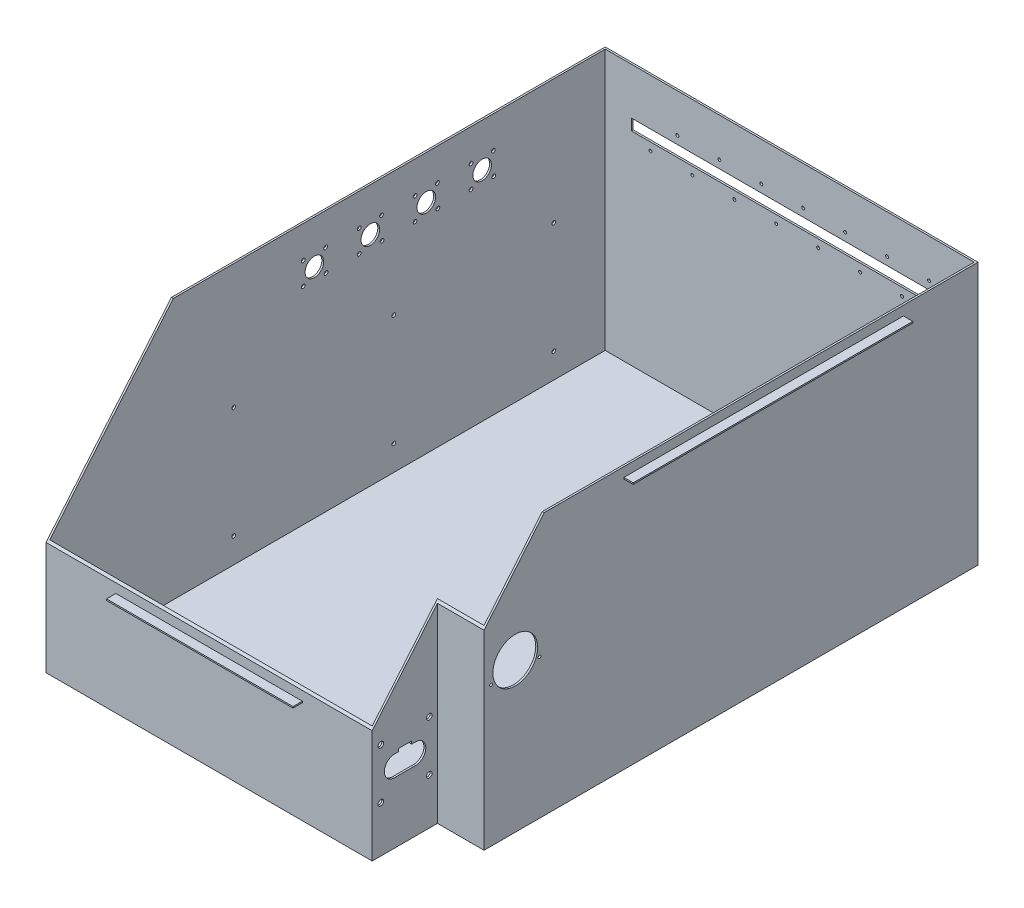
SolidWorks part; units mm, degrees
ref_plane "Front Plane" through (0, 0, 0) normal (0, 0, 1) x (1, 0, 0)
ref_plane "Top Plane" through (0, 0, 0) normal (0, 1, 0) x (1, 0, 0)
ref_plane "Right Plane" through (0, 0, 0) normal (1, 0, 0) x (0, 0, -1)
sketch "Sketch1" plane through (0, 0, 0) normal (0, 1, 0) x (1, 0, 0)
  line L1 (-200, 237.8263) -> (200, 237.8263)
  line L2 (-200, 237.8263) -> (-200, -362.1737)
  line L3 (-200, -362.1737) -> (150, -362.1737)
  line L4 (200, 237.8263) -> (200, -292.1737)
  line L6 (200, -292.1737) -> (150, -292.1737)
  line L7 (150, -292.1737) -> (150, -362.1737)
  line L8 (0, -55) -> (0, 55) construction
  point P1 (0, 237.8263)
  dimension "D1" = 600
  dimension "D2" = 400
  dimension "D5" = 70
  dimension "D6" = 50
extrude "Boss-Extrude1" add sketch "Sketch1" along normal blind 1.5
sketch "Sketch2" plane through (0, 1.5, 0) normal (0, 1, 0) x (1, 0, 0)
  line L60 (-198, 235.8263) -> (-198, -360.1737)
  line L61 (-198, -360.1737) -> (148, -360.1737)
  line L62 (148, -360.1737) -> (148, -290.1737)
  line L63 (148, -290.1737) -> (198, -290.1737)
  line L64 (198, -290.1737) -> (198, 235.8263)
  line L65 (198, 235.8263) -> (-198, 235.8263)
  line L66 (-200, 237.8263) -> (-200, -362.1737)
  line L67 (-200, -362.1737) -> (150, -362.1737)
  line L68 (150, -362.1737) -> (150, -292.1737)
  line L69 (150, -292.1737) -> (200, -292.1737)
  line L70 (200, -292.1737) -> (200, 237.8263)
  line L71 (200, 237.8263) -> (-200, 237.8263)
  line L72 (-200, 237.8263) -> (-200, -362.1737)
  line L73 (-200, -362.1737) -> (150, -362.1737)
  line L74 (150, -362.1737) -> (150, -292.1737)
  line L75 (150, -292.1737) -> (200, -292.1737)
  line L76 (200, -292.1737) -> (200, 237.8263)
  line L77 (200, 237.8263) -> (-200, 237.8263)
  dimension "D3" = 2
  dimension "D4" = 2
  dimension "D2" = 2
  dimension "D5" = 2
  dimension "D6" = 2
  dimension "D1" = 0
extrude "Boss-Extrude2" add sketch "Sketch2" along normal blind 280
sketch "Sketch3" plane through (-200, 0, 0) normal (-1, 0, 0) x (0, 0, 1)
  line L3 (362.1737, 281.5) -> (362.1737, 0) construction
  line L4 (362.1737, 121.1176) -> (227.5969, 281.5)
  line L6 (-237.8263, 281.5) -> (362.1737, 281.5) construction
  line L9 (362.1737, 281.5) -> (362.1737, 121.1176)
  line L10 (227.5969, 281.5) -> (362.1737, 281.5)
  dimension "D1" = 50
sketch "Sketch4" plane through (0, 0, -237.8263) normal (0, 0, -1) x (-1, 0, 0)
  line L0 (-200, 281.5) -> (-200, 0) construction
  line L1 (-200, 234.6761) -> (200, 234.6761)
  line L2 (-200, 234.6761) -> (-200, 192.2905)
  line L3 (-200, 192.2905) -> (200, 192.2905)
  line L4 (200, 234.6761) -> (200, 192.2905)
  line L5 (200, 281.5) -> (200, 0) construction
extrude "Boss-Extrude3" add sketch "Sketch4" against normal blind 2
extrude "Cut-Extrude1" cut sketch "Sketch3" against normal through all both and the other way through all
sketch "Sketch5" plane through (-200, 0, 0) normal (-1, 0, 0) x (0, 0, 1)
  line L0 (-115.8263, 223.1206) -> (-115.8263, 247.1206) construction
  line L5 (-115.8263, 223.1206) -> (-91.8263, 223.1206) construction
  line L6 (-115.8263, 247.1206) -> (-91.8263, 247.1206) construction
  line L7 (-91.8263, 223.1206) -> (-91.8263, 247.1206) construction
  line L8 (-115.8263, 223.1206) -> (-91.8263, 247.1206) construction
  line L9 (-115.8263, 247.1206) -> (-91.8263, 223.1206) construction
  line L10 (-55.8263, 223.1206) -> (-55.8263, 247.1206) construction
  line L11 (-55.8263, 223.1206) -> (-31.8263, 223.1206) construction
  line L12 (-55.8263, 247.1206) -> (-31.8263, 247.1206) construction
  line L13 (-31.8263, 223.1206) -> (-31.8263, 247.1206) construction
  line L14 (-55.8263, 223.1206) -> (-31.8263, 247.1206) construction
  line L15 (-55.8263, 247.1206) -> (-31.8263, 223.1206) construction
  line L16 (4.1737, 223.1206) -> (4.1737, 247.1206) construction
  line L17 (4.1737, 223.1206) -> (28.1737, 223.1206) construction
  line L18 (4.1737, 247.1206) -> (28.1737, 247.1206) construction
  line L19 (28.1737, 223.1206) -> (28.1737, 247.1206) construction
  line L20 (4.1737, 223.1206) -> (28.1737, 247.1206) construction
  line L21 (4.1737, 247.1206) -> (28.1737, 223.1206) construction
  line L22 (64.1737, 223.1206) -> (64.1737, 247.1206) construction
  line L23 (64.1737, 223.1206) -> (88.1737, 223.1206) construction
  line L24 (64.1737, 247.1206) -> (88.1737, 247.1206) construction
  line L25 (88.1737, 223.1206) -> (88.1737, 247.1206) construction
  line L26 (64.1737, 223.1206) -> (88.1737, 247.1206) construction
  line L27 (64.1737, 247.1206) -> (88.1737, 223.1206) construction
  line L28 (-235.8263, 281.5) -> (-235.8263, 1.5) construction
  circle A0 centre (-115.8263, 247.1206) radius 2
  circle A1 centre (-116.3263, 223.1259) radius 2
  circle A2 centre (-91.8263, 223.1206) radius 2
  circle A3 centre (-91.8263, 247.1206) radius 2
  circle A4 centre (-103.8263, 235.1206) radius 10
  circle A5 centre (-55.8263, 247.1206) radius 2
  circle A6 centre (-56.3263, 223.1259) radius 2
  circle A7 centre (-31.8263, 223.1206) radius 2
  circle A8 centre (-31.8263, 247.1206) radius 2
  circle A9 centre (-43.8263, 235.1206) radius 10
  circle A10 centre (4.1737, 247.1206) radius 2
  circle A11 centre (3.6737, 223.1259) radius 2
  circle A12 centre (28.1737, 223.1206) radius 2
  circle A13 centre (28.1737, 247.1206) radius 2
  circle A14 centre (16.1737, 235.1206) radius 10
  circle A15 centre (64.1737, 247.1206) radius 2
  circle A16 centre (63.6737, 223.1259) radius 2
  circle A17 centre (88.1737, 223.1206) radius 2
  circle A18 centre (88.1737, 247.1206) radius 2
  circle A19 centre (76.1737, 235.1206) radius 10
  point P9 (-103.8263, 235.1206)
  point P24 (-43.8263, 235.1206)
  point P38 (16.1737, 235.1206)
  point P52 (76.1737, 235.1206)
  dimension "D2" = 20
  dimension "D5" = 4
  dimension "D1" = 24
  dimension "D3" = 24
  dimension "D4" = 24
  dimension "D7" = 120
  dimension "D6" = 4
sketch "Sketch6" plane through (-198, 0, 0) normal (1, 0, 0) x (0, 0, -1)
  arc A0 (151.1392, 167.4539) -> (156.7272, 167.4539) centre (153.9332, 167.4539) ccw construction
  arc A1 (-68.8756, 167.4539) -> (-63.2876, 167.4539) centre (-66.0816, 167.4539) ccw construction
  arc A2 (-178.883, 167.4539) -> (-173.295, 167.4539) centre (-176.089, 167.4539) ccw construction
  arc A3 (151.1392, 167.4539) -> (156.7272, 167.4539) centre (153.9332, 167.4539) ccw
  arc A4 (-68.8756, 167.4539) -> (-63.2876, 167.4539) centre (-66.0816, 167.4539) ccw
  arc A5 (-178.883, 167.4539) -> (-173.295, 167.4539) centre (-176.089, 167.4539) ccw
  circle A6 centre (-176.089, 167.4539) radius 2.794
  circle A7 centre (-176.089, 167.4539) radius 4.5
  circle A8 centre (-64.4633, 167.4539) radius 4.5
  circle A9 centre (-64.4633, 167.4539) radius 2.794
  circle A10 centre (155.5515, 167.4539) radius 2.794
  circle A11 centre (155.5515, 167.4539) radius 4.5
  dimension "D1" = 9
extrude "Boss-Extrude4" [suppressed] add sketch "Sketch6" along normal blind 50 contours A4 A9 | A8 | A7 | A6 | A11 | A10
sketch "Sketch8" plane through (-198, 0, 0) normal (1, 0, 0) x (0, 0, -1)
  line L0 (235.8263, 1.5) -> (-360.1737, 1.5) construction
  line L1 (-360.1737, 123.5011) -> (-360.1737, 1.5) construction
  circle A0 centre (-265.6737, 172.1992) radius 2.39
  circle A1 centre (-265.6737, 172.1992) radius 4.39
  circle A2 centre (-265.1737, 16.5) radius 2.39
  circle A3 centre (-265.1737, 16.5) radius 4.39
  dimension "D3" = 4.78
  dimension "D4" = 2
  dimension "D1" = 155.7
  dimension "D2" = 15
  dimension "D5" = 95
extrude "Boss-Extrude5" [suppressed] add sketch "Sketch8" along normal blind 15
sketch "Sketch10" plane through (148, 0, 0) normal (-1, 0, 0) x (0, 0, 1)
  line L0 (315.6737, 86.5) -> (320.9237, 86.5) construction
  line L1 (315.6737, 66.5) -> (338.1737, 66.5) construction
  line L2 (338.1737, 76.5) -> (315.6737, 76.5) construction
  line L3 (360.1737, 1.5) -> (290.1737, 1.5) construction
  line L5 (320.9237, 86.5) -> (320.9237, 89.5) construction
  line L6 (320.9237, 89.5) -> (332.9237, 89.5) construction
  line L7 (332.9237, 86.5) -> (332.9237, 89.5) construction
  line L8 (360.1737, 123.5011) -> (360.1737, 1.5) construction
  line L9 (332.9237, 86.5) -> (338.1737, 86.5) construction
  line L10 (319.9237, 90.5) -> (333.9237, 90.5)
  line L11 (333.9237, 87.5) -> (333.9237, 90.5)
  line L12 (333.9237, 87.5) -> (338.1737, 87.5)
  line L13 (315.6737, 65.5) -> (338.1737, 65.5)
  line L14 (315.6737, 87.5) -> (319.9237, 87.5)
  line L15 (319.9237, 87.5) -> (319.9237, 90.5)
  line L17 (300.9737, 49.55) -> (352.8737, 49.55) construction
  line L18 (300.9737, 49.55) -> (300.9737, 103.45) construction
  line L19 (300.9737, 103.45) -> (352.8737, 103.45) construction
  line L20 (352.8737, 49.55) -> (352.8737, 103.45) construction
  line L21 (300.9737, 49.55) -> (352.8737, 103.45) construction
  line L22 (300.9737, 103.45) -> (352.8737, 49.55) construction
  arc A0 (315.6737, 86.5) -> (315.6737, 66.5) centre (315.6737, 76.5) ccw construction
  arc A1 (338.1737, 66.5) -> (338.1737, 86.5) centre (338.1737, 76.5) ccw construction
  arc A2 (338.1737, 65.5) -> (338.1737, 87.5) centre (338.1737, 76.5) ccw
  arc A3 (315.6737, 87.5) -> (315.6737, 65.5) centre (315.6737, 76.5) ccw
  circle A4 centre (300.9737, 103.45) radius 3
  circle A5 centre (352.8737, 103.45) radius 3
  circle A6 centre (300.9737, 49.55) radius 3
  circle A7 centre (352.8737, 49.55) radius 3
  point P12 (326.9237, 89.5)
  point P13 (326.9237, 76.5)
  point P26 (326.9237, 76.5)
  dimension "D1" = 65
  dimension "D2" = 22.5
  dimension "D6" = 20
  dimension "D10" = 6
  dimension "D3" = 22
  dimension "D4" = 12
  dimension "D5" = 3
  dimension "D8" = 51.9
  dimension "D9" = 53.9
  dimension "D7" = 1
extrude "Cut-Extrude2" cut sketch "Sketch10" against normal up to surface (2 mm away) contours L0 L7 L6 L5 | L2 A1 L0 A0 | A1 L2 A0 L1 | A0 | A1 | L14 A3 L13 A2 L12 L11 L10 L15 | A4 | A5 | A7 | A6 region at (148, 77.0724, 326.9237) region at (148, 103.45, 300.9737) region at (148, 103.45, 352.8737) region at (148, 49.55, 352.8737) up to face at (150, 81.4145, 327.1737)
sketch "Sketch11" plane through (148, 0, 0) normal (-1, 0, 0) x (0, 0, 1)
  line L0 (298.4737, 103.43) -> (298.4737, 49.53) construction
  line L13 (315.6737, 66.5) -> (338.1737, 66.5) construction
  line L14 (315.6737, 86.5) -> (320.9237, 86.5) construction
  line L15 (315.6737, 66.5) -> (338.1737, 66.5)
  line L19 (315.6737, 86.5) -> (318.4237, 86.5)
  line L20 (333.9237, 90.5) -> (319.9237, 90.5)
  line L21 (333.9237, 90.5) -> (319.9237, 90.5)
  line L22 (333.9237, 87.5) -> (333.9237, 90.5)
  line L23 (333.9237, 87.5) -> (333.9237, 90.5)
  line L28 (330.4237, 86.5) -> (320.9237, 86.5)
  line L29 (315.7815, 66) -> (338.2021, 66)
  line L30 (330.9237, 86) -> (320.2852, 86)
  line L31 (330.9237, 86) -> (330.9237, 91)
  line L32 (330.9237, 91) -> (317.9237, 91)
  line L33 (317.9237, 91) -> (317.9237, 87)
  line L34 (315.7815, 87) -> (317.9237, 87)
  line L36 (298.4737, 103.43) -> (350.3737, 103.43) construction
  line L43 (333.9237, 90.5) -> (319.9237, 90.5)
  line L44 (333.9237, 90.5) -> (319.9237, 90.5)
  line L45 (333.9237, 87.5) -> (333.9237, 90.5)
  line L46 (333.9237, 87.5) -> (333.9237, 90.5)
  line L47 (338.1737, 87.5) -> (333.9237, 87.5)
  line L48 (338.1737, 87.5) -> (333.9237, 87.5)
  line L49 (315.6737, 65.5) -> (338.1737, 65.5)
  line L50 (315.6737, 65.5) -> (338.1737, 65.5)
  line L51 (319.9237, 87.5) -> (315.6737, 87.5)
  line L52 (319.9237, 87.5) -> (315.6737, 87.5)
  line L53 (319.9237, 90.5) -> (319.9237, 87.5)
  line L54 (319.9237, 90.5) -> (319.9237, 87.5)
  line L55 (333.9237, 90.5) -> (319.9237, 90.5)
  line L56 (333.9237, 90.5) -> (319.9237, 90.5)
  line L57 (333.9237, 87.5) -> (333.9237, 90.5)
  line L58 (333.9237, 87.5) -> (333.9237, 90.5)
  line L59 (338.1737, 87.5) -> (333.9237, 87.5)
  line L60 (338.1737, 87.5) -> (333.9237, 87.5)
  line L61 (315.6737, 65.5) -> (338.1737, 65.5)
  line L62 (315.6737, 65.5) -> (338.1737, 65.5)
  line L63 (319.9237, 87.5) -> (315.6737, 87.5)
  line L64 (319.9237, 87.5) -> (315.6737, 87.5)
  line L65 (319.9237, 90.5) -> (319.9237, 87.5)
  line L66 (319.9237, 90.5) -> (319.9237, 87.5)
  line L67 (330.4237, 86.5) -> (330.4237, 90.5) construction
  line L68 (330.4237, 90.5) -> (318.4237, 90.5) construction
  line L69 (318.4237, 90.5) -> (318.4237, 86.5) construction
  line L70 (338.1737, 87.5) -> (333.9237, 87.5)
  line L71 (338.1737, 87.5) -> (333.9237, 87.5)
  line L72 (315.6737, 65.5) -> (338.1737, 65.5)
  line L73 (315.6737, 65.5) -> (338.1737, 65.5)
  line L74 (319.9237, 87.5) -> (315.6737, 87.5)
  line L75 (319.9237, 87.5) -> (315.6737, 87.5)
  line L76 (319.9237, 90.5) -> (319.9237, 87.5)
  line L77 (319.9237, 90.5) -> (319.9237, 87.5)
  arc A4 (338.2021, 66) -> (320.2852, 86) centre (336.3485, 82.3648) ccw
  arc A5 (338.1737, 65.5) -> (338.1737, 87.5) centre (338.1737, 76.5) ccw
  arc A7 (338.1737, 65.5) -> (338.1737, 87.5) centre (338.1737, 76.5) ccw
  arc A9 (315.7815, 87) -> (315.7815, 66) centre (311.0911, 76.5) ccw
  circle A10 centre (298.4737, 103.43) radius 3
  circle A11 centre (298.4737, 49.53) radius 3
  circle A12 centre (350.3737, 103.43) radius 3
  circle A13 centre (350.3737, 49.53) radius 3
  arc A16 (338.1737, 66.5) -> (320.9237, 86.5) centre (336.3485, 82.3648) ccw construction
  arc A17 (338.1737, 65.5) -> (338.1737, 87.5) centre (338.1737, 76.5) ccw
  arc A18 (315.6737, 87.5) -> (315.6737, 65.5) centre (315.6737, 76.5) ccw
  arc A19 (315.6737, 87.5) -> (315.6737, 65.5) centre (315.6737, 76.5) ccw
  arc A20 (315.6737, 86.5) -> (315.6737, 66.5) centre (311.0911, 76.5) ccw construction
  arc A21 (338.1737, 65.5) -> (338.1737, 87.5) centre (338.1737, 76.5) ccw
  arc A22 (315.6737, 87.5) -> (315.6737, 65.5) centre (315.6737, 76.5) ccw
  arc A23 (315.6737, 87.5) -> (315.6737, 65.5) centre (315.6737, 76.5) ccw
  arc A24 (338.1737, 65.5) -> (338.1737, 87.5) centre (338.1737, 76.5) ccw
  arc A25 (338.1737, 65.5) -> (338.1737, 87.5) centre (338.1737, 76.5) ccw
  arc A26 (315.6737, 87.5) -> (315.6737, 65.5) centre (315.6737, 76.5) ccw
  arc A27 (315.6737, 87.5) -> (315.6737, 65.5) centre (315.6737, 76.5) ccw
  dimension "D5" = 6
  dimension "D6" = 51.9
  dimension "D7" = 53.9
  dimension "D1" = 0
  dimension "D2" = 0
  dimension "D3" = 0
  dimension "D4" = 0.5
extrude "Cut-Extrude3" [suppressed] cut sketch "Sketch11" against normal through all
sketch "Sketch14" plane through (148, 0, 0) normal (-1, 0, 0) x (0, 0, 1)
  line L0 (362.1737, 121.1176) -> (362.1737, 0) construction
  line L1 (362.1737, 0) -> (292.1737, 0) construction
  circle A0 centre (297.2737, 103.43) radius 3
  circle A1 centre (349.1737, 103.43) radius 3
  circle A2 centre (349.1737, 49.53) radius 3
  circle A3 centre (297.2737, 49.53) radius 3
  dimension "D5" = 6
  dimension "D1" = 51.9
  dimension "D2" = 53.9
  dimension "D3" = 13
  dimension "D4" = 103.43
extrude "Cut-Extrude4" [suppressed] cut sketch "Sketch14" against normal up to surface (1.5 mm away) up to face at (150, 49.55, 303.9737)
sketch "Sketch15" plane through (198, 0, 0) normal (-1, 0, 0) x (0, 0, 1)
  line L1 (-223.8263, 252.1363) -> (-208.8263, 252.1363)
  line L2 (-223.8263, 252.1363) -> (-223.8263, 250.6363)
  line L3 (-223.8263, 250.6363) -> (-208.8263, 250.6363)
  line L4 (-208.8263, 252.1363) -> (-208.8263, 250.6363)
  line L5 (-235.8263, 281.5) -> (-235.8263, 1.5) construction
  line L6 (196.1737, 252.1363) -> (211.1737, 252.1363)
  line L7 (196.1737, 250.6363) -> (211.1737, 250.6363)
  line L8 (196.1737, 252.1363) -> (196.1737, 250.6363)
  line L9 (211.1737, 252.1363) -> (211.1737, 250.6363)
  dimension "D1" = 1.5
  dimension "D2" = 15
  dimension "D3" = 12
  dimension "D4" = 432
  dimension "D5" = 15
extrude "Boss-Extrude6" [suppressed] add sketch "Sketch15" along normal blind 15
ref_plane "Plane1" [suppressed] through (0, 0, -203.8263) normal (0, 0, -1) x (-1, 0, 0)
sketch "Sketch17" [suppressed] plane through (0, 0, -208.8263) normal (0, 0, 1) x (1, 0, 0)
  line L0 (198, 250.6363) -> (198, 235.6363)
  line L1 (198, 281.5) -> (198, 207.307) construction
  line L2 (198, 235.6363) -> (183, 250.6363)
  line L3 (183, 250.6363) -> (198, 250.6363)
  dimension "D1" = 15
extrude "Boss-Extrude7" [suppressed] add sketch "Sketch17" against normal blind 1.5
ref_plane "Plane2" [suppressed] through (0, 0, 191.1737) normal (0, 0, 1) x (1, 0, 0)
sketch "Sketch18" [suppressed] plane through (0, 0, 196.1737) normal (0, 0, 1) x (1, 0, 0)
  line L0 (198, 250.6363) -> (198, 235.6363)
  line L1 (198, 281.5) -> (198, 207.307) construction
  line L2 (198, 235.6363) -> (183, 250.6363)
  line L3 (183, 250.6363) -> (198, 250.6363)
  dimension "D1" = 15
extrude "Boss-Extrude8" [suppressed] add sketch "Sketch18" along normal blind 1.5
sketch "Sketch20" [suppressed] plane through (0, 252.1363, 0) normal (0, 1, 0) x (1, 0, 0)
  line L1 (183, 223.8263) -> (198, 223.8263) construction
  line L2 (183, 208.8263) -> (183, 223.8263) construction
  line L3 (183, -211.1737) -> (198, -211.1737) construction
  line L4 (183, -211.1737) -> (183, -196.1737) construction
  circle A0 centre (190.5, 216.3263) radius 2.4159
  circle A1 centre (190.5, -203.6737) radius 2
  dimension "D3" = 4
  dimension "D1" = 7.5
  dimension "D2" = 7.5
  dimension "D4" = 7.5
  dimension "D5" = 7.5
extrude "Cut-Extrude5" [suppressed] cut sketch "Sketch20" against normal up to surface (1.5 mm away)
extrude "Cut-Extrude7" cut sketch "Sketch5" against normal up to surface (2 mm away) up to face at (-198, 137.9002, 95.2583)
sketch "Sketch21" plane through (0, 0, -237.8263) normal (0, 0, -1) x (-1, 0, 0)
  line L0 (-200, 281.5) -> (200, 281.5) construction
  line L1 (-150, 271.5) -> (150, 271.5)
  line L2 (-150, 271.5) -> (-150, 270)
  line L3 (-150, 270) -> (150, 270)
  line L4 (150, 271.5) -> (150, 270)
  point P6 (0, 281.5)
  point P7 (0, 271.5)
  dimension "D1" = 1.5
  dimension "D2" = 300
  dimension "D3" = 10
extrude "Boss-Extrude9" add sketch "Sketch21" along normal blind 10
sketch "Sketch22" plane through (-200, 0, 0) normal (-1, 0, 0) x (0, 0, 1)
  line L0 (-237.8263, 281.5) -> (227.5969, 281.5) construction
  line L1 (-157.8263, 271.5) -> (142.1737, 271.5)
  line L2 (-157.8263, 271.5) -> (-157.8263, 270)
  line L3 (-157.8263, 270) -> (142.1737, 270)
  line L4 (142.1737, 271.5) -> (142.1737, 270)
  line L5 (-237.8263, 281.5) -> (-237.8263, 0) construction
  dimension "D1" = 1.5
  dimension "D2" = 10
  dimension "D3" = 80
  dimension "D4" = 300
extrude "Boss-Extrude10" add sketch "Sketch22" along normal blind 10
ref_plane "Plane3" through (0, 0, -77.8263) normal (0, 0, -1) x (-1, 0, 0)
sketch "Sketch23" plane through (0, 0, -77.8263) normal (0, 0, -1) x (-1, 0, 0)
  line L0 (210, 270) -> (200, 270) construction
  line L1 (210, 270) -> (200, 270)
  line L2 (210, 270) -> (200, 260)
  line L3 (200, 281.5) -> (200, 0) construction
  line L4 (200, 260) -> (200, 270)
  dimension "D1" = 10
extrude "Boss-Extrude11" add sketch "Sketch23" along normal mid plane 1.5
ref_plane "Plane4" through (0, 0, 52.1737) normal (0, 0, 1) x (1, 0, 0)
sketch "Sketch24" plane through (0, 0, 52.1737) normal (0, 0, 1) x (1, 0, 0)
  line L6 (-210, 270) -> (-200, 260)
  line L7 (-200, 260) -> (-200, 270)
  line L8 (-200, 270) -> (-210, 270)
  line L9 (-210, 270) -> (-200, 260)
  line L10 (-200, 260) -> (-200, 270)
  line L11 (-200, 270) -> (-210, 270)
  dimension "D1" = 0
extrude "Boss-Extrude12" add sketch "Sketch24" along normal mid plane 1.5
ref_plane "Plane5" through (100, 0, 0) normal (1, 0, 0) x (0, 0, -1)
sketch "Sketch25" plane through (100, 0, 0) normal (1, 0, 0) x (0, 0, -1)
  line L0 (247.8263, 270) -> (237.8263, 270)
  line L1 (237.8263, 270) -> (237.8263, 260)
  line L2 (237.8263, 281.5) -> (237.8263, 0) construction
  line L3 (237.8263, 260) -> (247.8263, 270)
  dimension "D1" = 10
extrude "Boss-Extrude13" add sketch "Sketch25" along normal mid plane 1.5
ref_plane "Plane6" through (-100, 0, 0) normal (-1, 0, 0) x (0, 0, 1)
sketch "Sketch26" plane through (-100, 0, 0) normal (-1, 0, 0) x (0, 0, 1)
  line L3 (-247.8263, 270) -> (-237.8263, 260)
  line L4 (-237.8263, 260) -> (-237.8263, 270)
  line L5 (-237.8263, 270) -> (-247.8263, 270)
  line L6 (-247.8263, 270) -> (-237.8263, 260)
  line L7 (-237.8263, 260) -> (-237.8263, 270)
  line L8 (-237.8263, 270) -> (-247.8263, 270)
  dimension "D1" = 0
extrude "Boss-Extrude14" add sketch "Sketch26" along normal mid plane 1.5
mirror "Mirror1" about plane through (0, 0, 0) normal (1, 0, 0) of "Boss-Extrude11", "Boss-Extrude12", "Boss-Extrude10"
sketch "Sketch27" plane through (0, 0, 362.1737) normal (0, 0, 1) x (1, 0, 0)
  line L0 (150, 121.1176) -> (-200, 121.1176) construction
  line L1 (-125, 111.1176) -> (75, 111.1176)
  line L2 (-125, 111.1176) -> (-125, 109.6176)
  line L3 (-125, 109.6176) -> (75, 109.6176)
  line L4 (75, 111.1176) -> (75, 109.6176)
  line L5 (150, 121.1176) -> (-200, 121.1176) construction
  point P6 (-25, 121.1176)
  point P7 (-25, 111.1176)
  dimension "D1" = 1.5
  dimension "D2" = 200
  dimension "D3" = 10
extrude "Boss-Extrude15" add sketch "Sketch27" along normal blind 10
ref_plane "Plane7" through (-95, 0, 0) normal (-1, 0, 0) x (0, 0, 1)
sketch "Sketch28" plane through (-95, 0, 0) normal (-1, 0, 0) x (0, 0, 1)
  line L0 (372.1737, 109.6176) -> (362.1737, 109.6176)
  line L1 (362.1737, 109.6176) -> (362.1737, 99.6176)
  line L2 (362.1737, 121.1176) -> (362.1737, 0) construction
  line L3 (362.1737, 99.6176) -> (372.1737, 109.6176)
  dimension "D1" = 10
extrude "Boss-Extrude16" add sketch "Sketch28" along normal mid plane 1.5
ref_plane "Plane8" through (45, 0, 0) normal (1, 0, 0) x (0, 0, -1)
sketch "Sketch29" plane through (45, 0, 0) normal (1, 0, 0) x (0, 0, -1)
  line L3 (-372.1737, 109.6176) -> (-362.1737, 99.6176)
  line L4 (-362.1737, 99.6176) -> (-362.1737, 109.6176)
  line L5 (-362.1737, 109.6176) -> (-372.1737, 109.6176)
  line L6 (-372.1737, 109.6176) -> (-362.1737, 99.6176)
  line L7 (-362.1737, 99.6176) -> (-362.1737, 109.6176)
  line L8 (-362.1737, 109.6176) -> (-372.1737, 109.6176)
  dimension "D1" = 0
extrude "Boss-Extrude17" add sketch "Sketch29" along normal mid plane 1.5
sketch "Sketch30" plane through (200, 0, 0) normal (1, 0, 0) x (0, 0, -1)
  line L1 (-292.1737, 0) -> (237.8263, 0) construction
  line L2 (-292.1737, 204.5403) -> (-292.1737, 0) construction
  circle A0 centre (-258.6737, 160) radius 24
  circle A1 centre (-284.6737, 150) radius 1.5
  circle A2 centre (-232.6737, 150) radius 1.5
  dimension "D1" = 48
  dimension "D2" = 3
  dimension "D3" = 3
  dimension "D4" = 26
  dimension "D5" = 10
  dimension "D6" = 26
  dimension "D7" = 10
  dimension "D8" = 160
  dimension "D9" = 33.5
extrude "Cut-Extrude8" cut sketch "Sketch30" against normal up to surface (2 mm away) up to face at (198, 154.5848, 67.2583)
sketch "Sketch33" plane through (-200, 0, 0) normal (-1, 0, 0) x (0, 0, 1)
  line L0 (-237.8263, 281.5) -> (-237.8263, 0) construction
  line L1 (-237.8263, 0) -> (362.1737, 0) construction
  circle A0 centre (-180.6263, 147.77) radius 2
  circle A1 centre (-180.6263, 28.39) radius 2
  circle A2 centre (-8.9263, 147.77) radius 2
  circle A3 centre (-8.9263, 28.39) radius 2
  circle A4 centre (162.7737, 147.77) radius 2
  circle A5 centre (162.7737, 28.39) radius 2
  dimension "D3" = 4
  dimension "D1" = 57.2
  dimension "D2" = 119.38
  dimension "D4" = 28.39
  dimension "D5" = 3
extrude "Cut-Extrude9" cut sketch "Sketch33" against normal up to surface (2 mm away) up to face at (-198, 223.1206, 26.1737)
sketch "Sketch42" plane through (0, 0, -235.8263) normal (0, 0, 1) x (1, 0, 0)
  line L8 (200, 281.5) -> (-200, 281.5) construction
  line L9 (170, 219.5) -> (-170, 219.5)
  line L10 (170, 219.5) -> (170, 231.5)
  line L11 (170, 231.5) -> (-170, 231.5)
  line L12 (-170, 219.5) -> (-170, 231.5)
  line L15 (200, 225.5) -> (-200, 225.5) construction
  line L16 (200, 281.5) -> (200, 0) construction
  line L17 (-200, 281.5) -> (-200, 0) construction
  line L18 (-72.5, 243) -> (-107.5, 243)
  line L19 (-117.5, 208) -> (-152.5, 208) construction
  line L20 (-117.5, 208) -> (-117.5, 243) construction
  line L21 (-117.5, 243) -> (-152.5, 243) construction
  line L22 (-152.5, 208) -> (-152.5, 243) construction
  line L25 (-72.5, 208) -> (-72.5, 243)
  line L26 (-107.5, 208) -> (-107.5, 243)
  line L27 (-72.5, 208) -> (-107.5, 208)
  line L29 (-27.5, 243) -> (-62.5, 243)
  line L30 (-27.5, 208) -> (-27.5, 243)
  line L31 (-62.5, 208) -> (-62.5, 243)
  line L32 (-27.5, 208) -> (-62.5, 208)
  line L34 (17.5, 243) -> (-17.5, 243)
  line L35 (17.5, 208) -> (17.5, 243)
  line L36 (-17.5, 208) -> (-17.5, 243)
  line L37 (17.5, 208) -> (-17.5, 208)
  line L39 (62.5, 243) -> (27.5, 243)
  line L40 (62.5, 208) -> (62.5, 243)
  line L41 (27.5, 208) -> (27.5, 243)
  line L42 (62.5, 208) -> (27.5, 208)
  line L44 (107.5, 243) -> (72.5, 243)
  line L45 (107.5, 208) -> (107.5, 243)
  line L46 (72.5, 208) -> (72.5, 243)
  line L47 (107.5, 208) -> (72.5, 208)
  line L49 (152.5, 243) -> (117.5, 243)
  line L50 (152.5, 208) -> (152.5, 243)
  line L51 (117.5, 208) -> (117.5, 243)
  line L52 (152.5, 208) -> (117.5, 208)
  circle A0 centre (-120.5, 240) radius 1.6
  circle A1 centre (-149.5, 211) radius 1.6
  circle A2 centre (-75.5, 240) radius 1.6
  circle A3 centre (-104.5, 211) radius 1.6
  circle A4 centre (-30.5, 240) radius 1.6
  circle A5 centre (-59.5, 211) radius 1.6
  circle A6 centre (14.5, 240) radius 1.6
  circle A7 centre (-14.5, 211) radius 1.6
  circle A8 centre (59.5, 240) radius 1.6
  circle A9 centre (30.5, 211) radius 1.6
  circle A10 centre (104.5, 240) radius 1.6
  circle A11 centre (75.5, 211) radius 1.6
  circle A12 centre (149.5, 240) radius 1.6
  circle A13 centre (120.5, 211) radius 1.6
  point P0 (0, 225.5)
  point P13 (-135, 225.5)
  dimension "D4" = 3
  dimension "D6" = 3
  dimension "D1" = 50
  dimension "D2" = 17.5
  dimension "D5" = 3
  dimension "D7" = 3
  dimension "D3" = 7
extrude "Cut-Extrude13" cut sketch "Sketch42" against normal blind 40 contours L10 L11 L12 L9 | A0 | A1 | A2 | A3 | A4 | A5 | A6 | A7 | A8 | A9 | A10 | A11 | A13 | A12
sketch "Sketch43" plane through (0, 0, 0) normal (0, -1, 0) x (1, 0, 0)
  line L0 (-200, 362.1737) -> (150, 362.1737) construction
  line L1 (150, 292.1737) -> (200, 292.1737)
  line L2 (150, 292.1737) -> (150, 362.1737)
  line L3 (150, 362.1737) -> (200, 362.1737)
  line L4 (200, 292.1737) -> (200, 362.1737)
  line L5 (200, 292.1737) -> (200, -237.8263) construction
